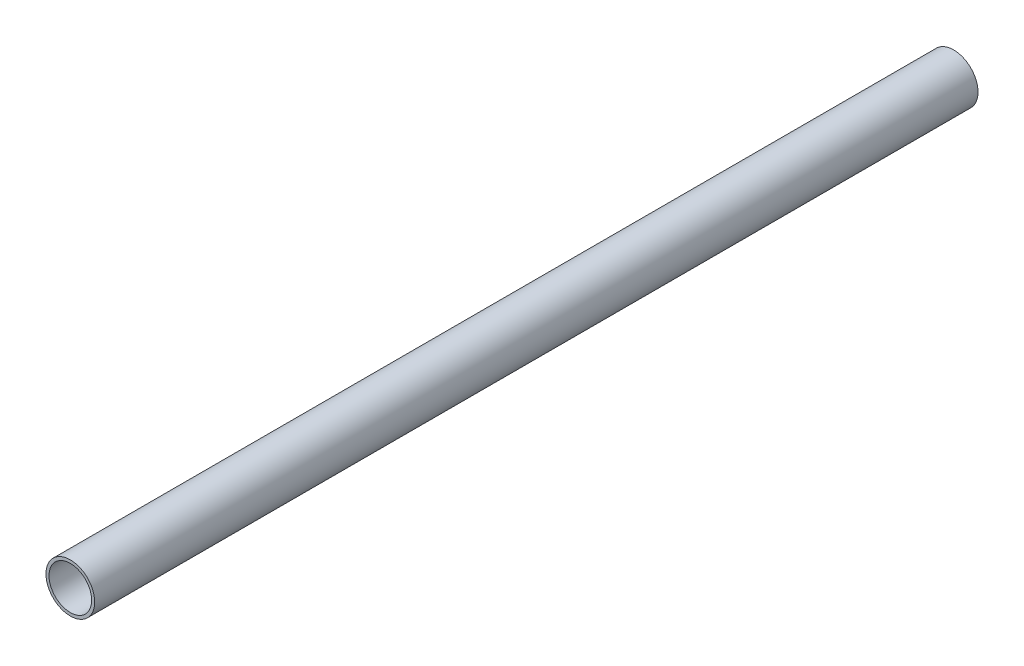
SolidWorks part; units mm, degrees
ref_plane "Front Plane" through (0, 0, 0) normal (0, 0, 1) x (1, 0, 0)
ref_plane "Top Plane" through (0, 0, 0) normal (0, 1, 0) x (1, 0, 0)
ref_plane "Right Plane" through (0, 0, 0) normal (1, 0, 0) x (0, 0, -1)
sketch "Sketch1" plane through (0, 0, 0) normal (0, 0, 1) x (1, 0, 0)
  circle A0 centre (0, 0) radius 7
  circle A1 centre (0, 0) radius 8
  dimension "D1" = 16
  dimension "D2" = 14
extrude "Boss-Extrude1" add sketch "Sketch1" along normal blind 260 and the other way blind 30
ref_axis "Assi1" through (0, 0, -30) along (0, 0, 1)
